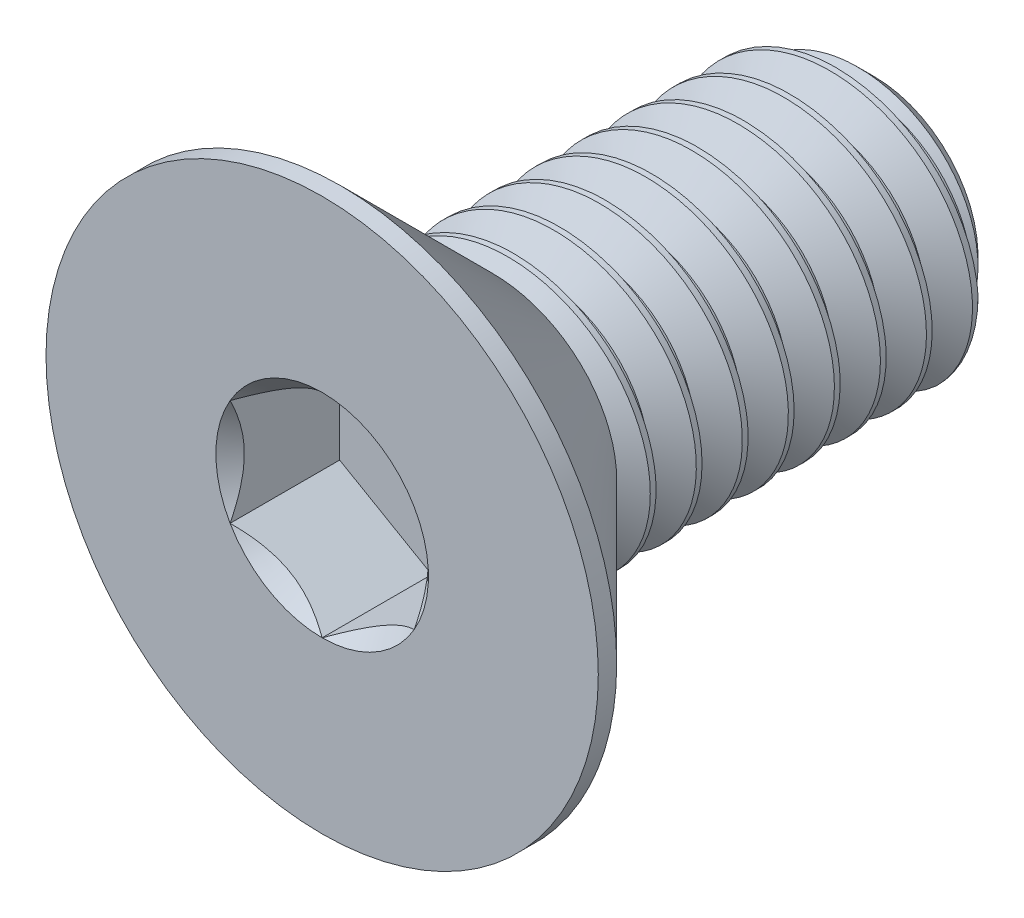
SolidWorks part; units mm, degrees
ref_plane "Front" through (0, 0, 0) normal (0, 0, 1) x (1, 0, 0)
ref_plane "Top" through (0, 0, 0) normal (0, 1, 0) x (1, 0, 0)
ref_plane "Right" through (0, 0, 0) normal (1, 0, 0) x (0, 0, -1)
sketch "Sketch1" plane through (0, 0, 0) normal (1, 0, 0) x (0, 0, -1)
  line L0 (0, 3) -> (0.2, 3) construction
  line L1 (0.2, 3) -> (1.7, 1.5) construction
  line L2 (0, 1.5) -> (6, 1.5)
  line L3 (6, 1.5) -> (6, 0)
  line L4 (6, 0) -> (0, 0)
  line L5 (0, 0) -> (0, 3) construction
  line L6 (0, 3) -> (0, -3) construction
  line L7 (6, 1.5) -> (6, -1.5) construction
  line L8 (0, -3) -> (0.2, -3) construction
  line L9 (0.2, -3) -> (1.7, -1.5) construction
  line L11 (0, 1.5) -> (0, 0)
  line L12 (1.7, 1.5) -> (1.7, 0) construction
  dimension "Head Ht" = 1.7
  dimension "Head Dia" = 6
  dimension "Dia" = 3
  dimension "Lg" = 6
  dimension "Head Angle" = 90
revolve "Revolve1" add sketch "Sketch1" angle 360 mid plane about L4
sketch "Sketch3" plane through (0, 0, -6) normal (0, 0, -1) x (-1, 0, 0)
  circle A0 centre (0, 0) radius 1.5
curve "Helix/Spiral1" pitch 0.5 height 6 radius 1.5 centre (0, 0, -6) axis (0, 0, 1) start towards (0, 1, 0)
sketch "Sketch2" plane through (0, 0, 0) normal (1, 0, 0) x (0, 0, -1)
  line L0 (6, 1.5) -> (6.4375, 1.5)
  line L1 (6.4375, 1.5) -> (6.25, 1.1752)
  line L2 (6.25, 1.1752) -> (6.1875, 1.1752)
  line L3 (6.1875, 1.1752) -> (6, 1.5)
  line L4 (6.0938, 1.3376) -> (6.3437, 1.3376) construction
  dimension "D1" = 60
  dimension "D2" = 0.0625
  dimension "D3" = 0.25
chamfer "Chamfer1" distance 0.375 angle 45 1 edges at (0, 1.5, -6)
sweep "Cut-Sweep1" cut profiles "Sketch2" path "Helix/Spiral1" align with end faces yes
sketch "Sketch7" plane through (0, 0, 0) normal (1, 0, 0) x (0, 0, -1)
  line L0 (0, 3) -> (0.2, 3) construction
  line L1 (0.2, 3) -> (1.7, 1.5) construction
  line L2 (0, 3) -> (0.2, 3)
  line L3 (0.2, 3) -> (1.7, 1.5)
  line L4 (1.7, 1.5) -> (1.7, 0) construction
  line L5 (1.7, 1.5) -> (1.7, 0)
  line L7 (0, 0) -> (0, 3) construction
  line L8 (0, 0) -> (0, 3)
  line L9 (0, 0) -> (1.7, 0)
  line L10 (3.3, 0) -> (-3.3, 0) construction
revolve "Revolve2" add sketch "Sketch7" angle 360 mid plane about L9
ref_plane "Plane1" through (0, 0, -1.7) normal (0, 0, 1) x (1, 0, 0)
sketch "Sketch8" plane through (0, 0, -1.7) normal (0, 0, 1) x (1, 0, 0)
  circle A0 centre (0, 0) radius 1.5
extrude "Boss-Extrude1" add sketch "Sketch8" against normal through all draft 45
sketch "Sketch5" plane through (0, 0, 0) normal (0, 0, 1) x (1, 0, 0)
  line L1 (1, -0.5774) -> (1, 0.5774)
  line L2 (1, 0.5774) -> (0, 1.1547)
  line L3 (0, 1.1547) -> (-1, 0.5774)
  line L4 (-1, 0.5774) -> (-1, -0.5774)
  line L5 (-1, -0.5774) -> (0, -1.1547)
  line L6 (0, -1.1547) -> (1, -0.5774)
  circle A0 centre (0, 0) radius 1 construction
  dimension "Hex" = 2
extrude "Cut-Extrude2" cut sketch "Sketch5" against normal blind 1.19
sketch "Sketch6" plane through (0, 0, 0) normal (0, 0, 1) x (1, 0, 0)
  circle A0 centre (0, 0) radius 1.1547
extrude "Cut-Extrude3" cut sketch "Sketch6" against normal blind 1.19 draft 45
sketch "Sketch9" [suppressed] plane through (0, 0, -5.5) normal (0, 0, 1) x (1, 0, 0)
  circle A1 centre (0, 0) radius 5
  circle A2 centre (0, 0) radius 5
  point P0 (0, 5)
  dimension "D1" = 0
extrude "Boss-Extrude2" [suppressed] add sketch "Sketch9" against normal offset from surface (18.5 mm away) 26 up to face at (0, 1.125, -6)
fillet "Fillet1" [suppressed] radius 0.3
sketch "Sketch10" plane through (0, 0, 0) normal (1, 0, 0) x (0, 0, -1)
  line L0 (6, 1.5) -> (6, -1.5) construction
  point P0 (5.25, -1.5)
  dimension "D1" = 0.75
equation "\"D3@Helix/Spiral1\" = \"Lg@Sketch1\""
equation "\"D2@Sketch2\" = \"D4@Helix/Spiral1\" * .125"
equation "\"D3@Sketch2\" = \"D4@Helix/Spiral1\" * .5"
equation "\"D1@Chamfer1\" = \"D4@Helix/Spiral1\" * .75"
equation "\"D1@Cut-Extrude2\" = \"Head Ht@Sketch1\" * .7"
equation "\"D1@Sketch10\" = \"D4@Helix/Spiral1\" * 1.5"
equation "\"D1@Cut-Extrude3\" = \"D1@Cut-Extrude2\""
equation "\"D1@Fillet1\" = \"Dia@Sketch1\" * .1"
